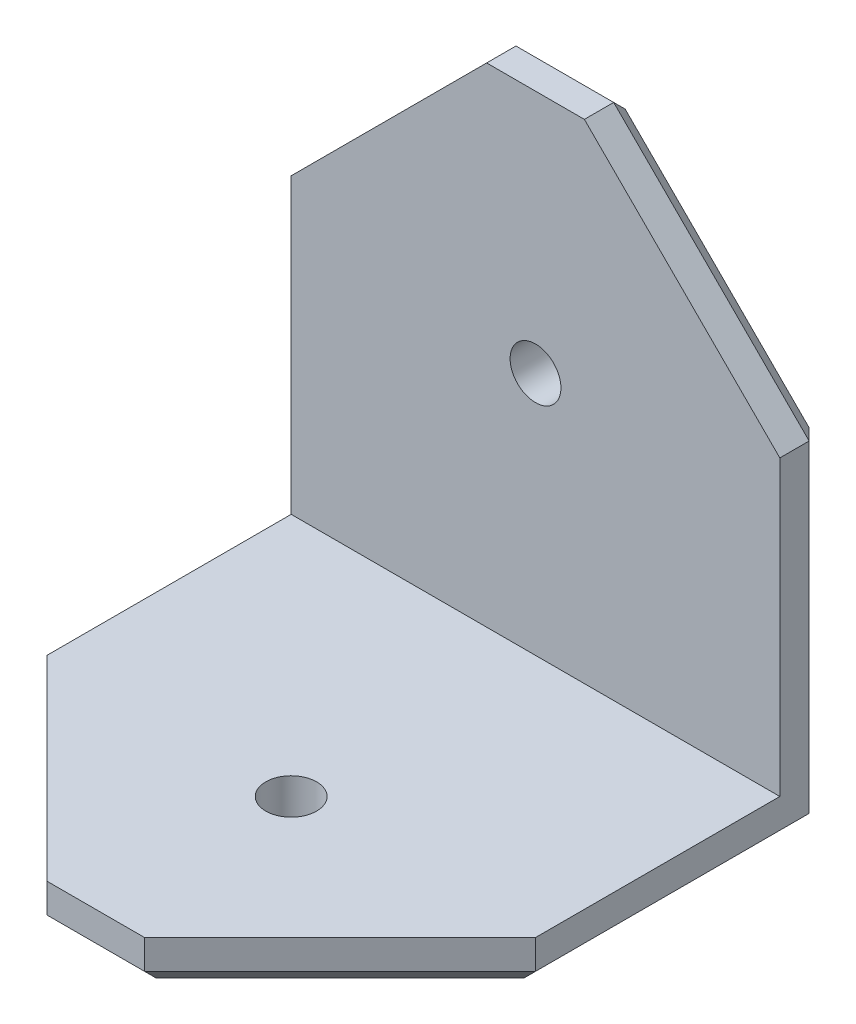
SolidWorks part; units mm, degrees
ref_plane "Front Plane" through (0, 0, 0) normal (0, 0, 1) x (1, 0, 0)
ref_plane "Top Plane" through (0, 0, 0) normal (0, 1, 0) x (1, 0, 0)
ref_plane "Right Plane" through (0, 0, 0) normal (1, 0, 0) x (0, 0, -1)
sketch "Sketch1" plane through (0, 0, 0) normal (0, 1, 0) x (1, 0, 0)
  line L1 (-25, 25) -> (25, 25)
  line L2 (-25, 25) -> (-25, -25)
  line L3 (-25, -25) -> (25, -25)
  line L4 (25, 25) -> (25, -25)
  line L5 (-25, 25) -> (25, -25) construction
  line L6 (-25, -25) -> (25, 25) construction
  point P0 (0, 0)
  dimension "D1" = 50
  dimension "D2" = 50
extrude "Boss-Extrude1" add sketch "Sketch1" along normal blind 5
sketch "Sketch2" plane through (0, 5, 0) normal (0, 1, 0) x (1, 0, 0)
  line L1 (-25, 20) -> (25, 20)
  line L2 (-25, 20) -> (-25, 25)
  line L3 (-25, 25) -> (25, 25)
  line L4 (25, 20) -> (25, 25)
  line L5 (-25, 20) -> (25, 25) construction
  line L6 (-25, 25) -> (25, 20) construction
  point P0 (0, 22.5)
  dimension "D1" = 5
extrude "Boss-Extrude2" add sketch "Sketch2" along normal blind 50
sketch "Sketch3" plane through (0, 0, -20) normal (0, 0, 1) x (1, 0, 0)
  line L0 (-25, 5) -> (25, 5) construction
  line L1 (0, 55) -> (0, 5) construction
  line L2 (-25, 55) -> (25, 55) construction
  circle A0 centre (0, 30) radius 2.6
  dimension "D1" = 25
  dimension "D2" = 5.2
extrude "Cut-Extrude1" cut sketch "Sketch3" against normal blind 50
chamfer "Chamfer1" distance 20 angle 45 2 edges at (25, 55, -22.5) (-25, 55, -22.5)
sketch "Sketch4" plane through (0, 5, 0) normal (0, 1, 0) x (1, 0, 0)
  line L0 (25, 20) -> (5, 20) construction
  line L1 (0, 20) -> (0, -25) construction
  line L2 (-5, 20) -> (5, 20) construction
  line L3 (-25, -25) -> (25, -25) construction
  circle A0 centre (0, -5) radius 2.6
  dimension "D1" = 25
  dimension "D2" = 5.2
extrude "Cut-Extrude2" cut sketch "Sketch4" against normal blind 50
chamfer "Chamfer2" distance 20 angle 45 2 edges at (25, 2.5, 25) (-25, 2.5, 25)
chamfer "Chamfer3" distance 2 angle 45 1 edges at (0, 0, -25)
chamfer "Chamfer4" distance 2 angle 45 10 edges at (25, 0, -9) (15, 0, 15) (0, 0, 25) (-15, 0, 15) (-25, 0, -9) (25, 18.5, -25) (15, 45, -25) (0, 55, -25) (-15, 45, -25) (-25, 18.5, -25)
